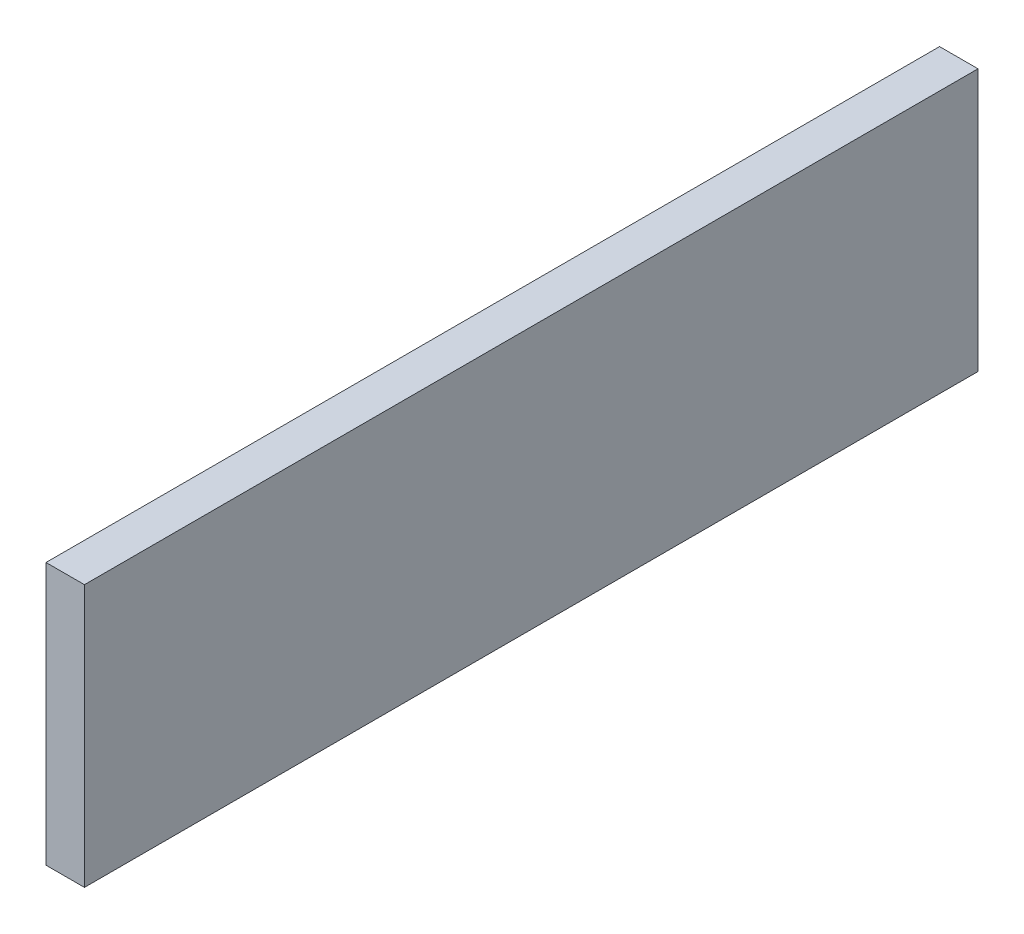
SolidWorks part; units mm, degrees
material "Aço 4140"
ref_plane "Plano frontal" through (0, 0, 0) normal (0, 0, 1) x (1, 0, 0)
ref_plane "Plano superior" through (0, 0, 0) normal (0, 1, 0) x (1, 0, 0)
ref_plane "Plano direito" through (0, 0, 0) normal (1, 0, 0) x (0, 0, -1)
sketch "Esboço1" plane through (0, 0, 0) normal (0, 0, 1) x (1, 0, 0)
  line L1 (-5.5, -37.5) -> (5.5, -37.5)
  line L2 (-5.5, -37.5) -> (-5.5, 37.5)
  line L3 (-5.5, 37.5) -> (5.5, 37.5)
  line L4 (5.5, -37.5) -> (5.5, 37.5)
  line L5 (-5.5, -37.5) -> (5.5, 37.5) construction
  line L6 (-5.5, 37.5) -> (5.5, -37.5) construction
  point P0 (0, 0)
  dimension "D1" = 75
  dimension "D2" = 11
extrude "Ressalto-extrusão1" add sketch "Esboço1" along normal blind 255.6
